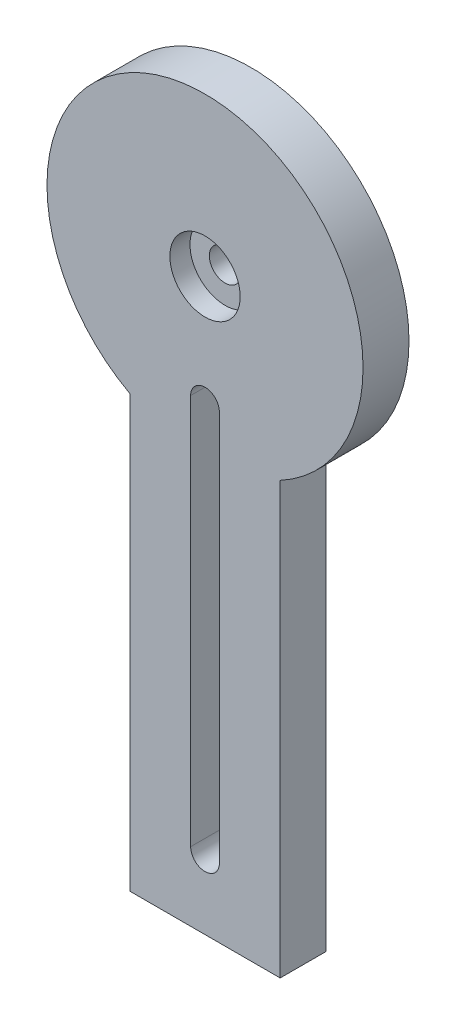
SolidWorks part; units mm, degrees
ref_plane "Piano frontale" through (0, 0, 0) normal (0, 0, 1) x (1, 0, 0)
ref_plane "Piano superiore" through (0, 0, 0) normal (0, 1, 0) x (1, 0, 0)
ref_plane "Piano destro" through (0, 0, 0) normal (1, 0, 0) x (0, 0, -1)
sketch "Schizzo1" plane through (0, 0, 0) normal (0, 0, 1) x (1, 0, 0)
  line L0 (0, 0) -> (0, 75)
  line L1 (0, 0) -> (26.16, 0)
  line L2 (26.16, 0) -> (26.16, 75)
  line L6 (0, 37.5) -> (13.08, 37.5) construction
  arc A1 (26.16, 75) -> (0, 75) centre (13.08, 99.1902) ccw
  dimension "D1" = 75
  dimension "D3" = 55
  dimension "D2" = 75
  dimension "D4" = 26.16
extrude "Estrusione-Estrusione1" add sketch "Schizzo1" along normal mid plane 8
sketch "Schizzo2" plane through (0, 0, 4) normal (0, 0, 1) x (1, 0, 0)
  line L0 (0, 37.5) -> (26.16, 37.5) construction
  line L1 (0, 75) -> (0, 0) construction
  line L2 (26.16, 0) -> (26.16, 75) construction
  line L3 (13.08, 0) -> (13.08, 99.1276) construction
  line L7 (0, 0) -> (26.16, 0) construction
  line L8 (13.08, 12) -> (13.08, 80) construction
  line L9 (10.58, 12) -> (10.58, 80)
  line L10 (15.58, 12) -> (15.58, 80)
  arc A3 (10.58, 12) -> (15.58, 12) centre (13.08, 12) ccw
  arc A4 (15.58, 80) -> (10.58, 80) centre (13.08, 80) ccw
  point P12 (13.08, 46)
  dimension "D1" = 2.5
  dimension "D3" = 80
  dimension "D2" = 12
extrude "Taglio-Estrusione1" cut sketch "Schizzo2" against normal through all
sketch "Schizzo11" plane through (0, 0, 4) normal (0, 0, 1) x (1, 0, 0)
  arc A0 (26.16, 75) -> (0, 75) centre (13.08, 99.1902) ccw construction
  arc A1 (26.16, 75) -> (0, 75) centre (13.08, 99.1902) ccw construction
hole_wizard "Foro lamato per Bullone M5 a testa esagonale-1" positions "Schizzo12" profile "Schizzo13" counterbore size "M5" standard "ISO" end condition through all
sketch "Schizzo12" plane through (0, 0, 4) normal (0, 0, 1) x (1, 0, 0)
  point P0 (13.08, 99.1902)
sketch "Schizzo13" plane through (13.08, 99.1902, 4) normal (1, 0, 0) x (0, -1, 0)
  line L0 (0, 0) -> (0, 8)
  line L1 (0, 8) -> (2.75, 8)
  line L3 (2.75, 8) -> (2.75, 3.5)
  line L4 (2.75, 3.5) -> (6.119, 3.5)
  line L5 (6.119, 3.5) -> (6.119, 0)
  line L7 (6.119, 0) -> (0, 0)
  line L11 (0, -6.35) -> (0, 107.95) construction
  dimension "Thru Hole Dia." = 5.5
  dimension "Thru Hole Depth" = 8
  dimension "C'Bore Dia." = 12.238
  dimension "C'Bore Depth" = 3.5
sketch "Schizzo15" plane through (0, 0, -4) normal (0, 0, -1) x (-1, 0, 0)
  line L0 (-10.58, 46) -> (-26.16, 46) construction
  line L1 (-10.58, 80) -> (-10.58, 12) construction
  line L2 (-26.16, 0) -> (-26.16, 75) construction
  line L3 (-26.16, 46) -> (-13.08, 0) construction
  line L4 (0, 0) -> (-26.16, 0) construction
  line L5 (-13.08, 0) -> (-13.08, 46) construction
